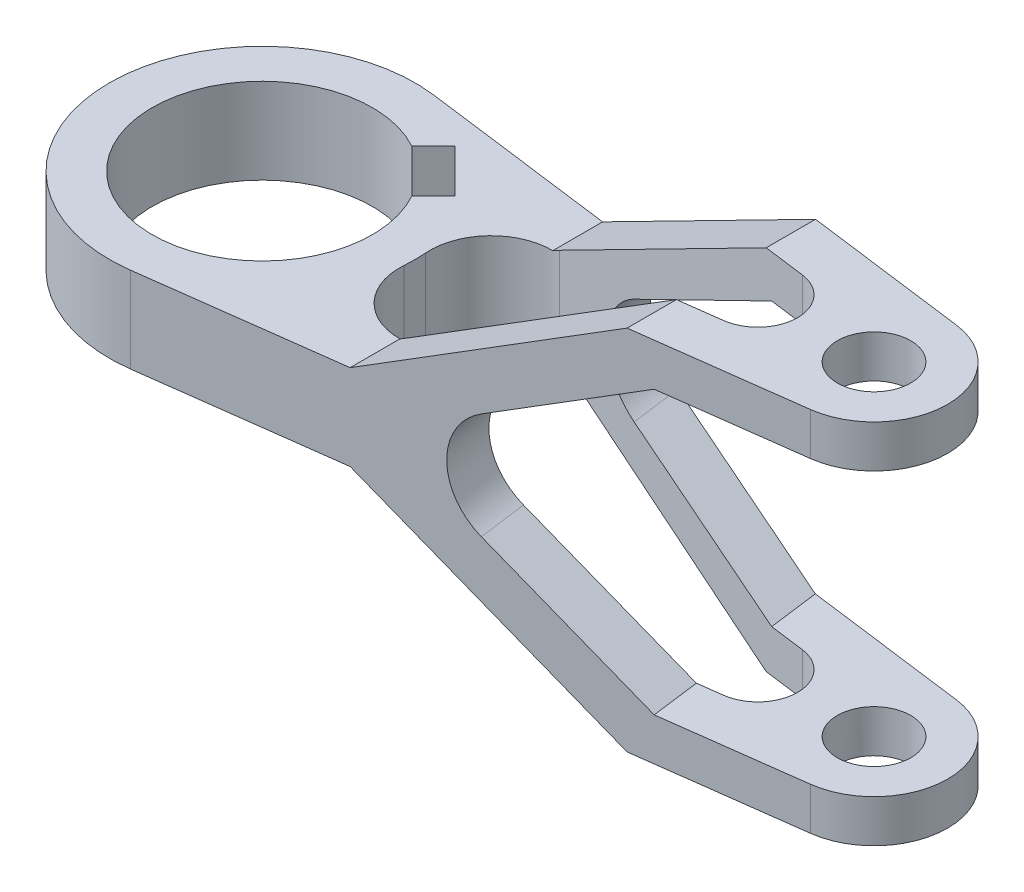
SolidWorks part; units mm, degrees
ref_plane "Front Plane" through (0, 0, 0) normal (0, 0, 1) x (1, 0, 0)
ref_plane "Top Plane" through (0, 0, 0) normal (0, 1, 0) x (1, 0, 0)
ref_plane "Right Plane" through (0, 0, 0) normal (1, 0, 0) x (0, 0, -1)
sketch "Sketch1" plane through (0, 0, 0) normal (0, 1, 0) x (1, 0, 0)
  line L0 (3.2407, 24.7891) -> (101.5604, 11.9355)
  line L1 (0, 0) -> (25, 0) construction
  line L2 (3.2407, -24.7891) -> (101.5604, -11.9355)
  line L3 (20.3793, 14.4804) -> (81.8426, 6.4452)
  line L4 (20.3793, -14.4804) -> (81.8426, -6.4452)
  line L5 (2.2037, 16.8566) -> (100.5233, 4.003) construction
  line L6 (2.2037, -16.8566) -> (100.5233, -4.003) construction
  line L7 (74.2692, 0) -> (88, 0) construction
  arc A0 (3.2407, 24.7891) -> (3.2407, -24.7891) centre (0, 0) ccw
  circle A2 centre (100, 0) radius 6
  circle A3 centre (0, 0) radius 18
  arc A4 (20.3793, -14.4804) -> (20.3793, 14.4804) centre (0, 0) ccw
  arc A5 (101.5604, -11.9355) -> (101.5604, 11.9355) centre (100, 0) ccw
  arc A6 (81.8426, -6.4452) -> (81.8426, 6.4452) centre (81, 0) ccw
  dimension "D2" = 50
  dimension "D3" = 19
  dimension "D4" = 36
  dimension "D5" = 12
  dimension "D8" = 13
  dimension "D1" = 100
  dimension "D6" = 8
  dimension "D7" = 8
extrude "Boss-Extrude2" add sketch "Sketch1" along normal blind 30 and the other way blind 30
sketch "Sketch3" plane through (0, 0, 0) normal (0, 0, 1) x (1, 0, 0)
  line L0 (-25, 7) -> (35, 7)
  line L1 (-25, 30) -> (-25, -30) construction
  line L2 (35, 7) -> (75.037, 30)
  line L3 (3.2407, 30) -> (101.5604, 30) construction
  line L4 (75.037, 30) -> (-25, 30)
  line L5 (-25, 30) -> (-25, 7)
  dimension "D1" = 7
  dimension "D2" = 60
  dimension "D3" = 37
extrude "Cut-Extrude1" cut sketch "Sketch3" against normal blind 30 and the other way up to next contours L4 L5 L0 L2
mirror "Mirror1" about plane through (0, 0, 0) normal (0, 1, 0) of "Cut-Extrude1"
sketch "Sketch4" plane through (3.2407, 0, 24.7891) normal (0.1296, 0, 0.9916) x (0.9916, 0, -0.1296)
  line L2 (35.9891, 0.0486) -> (76.3669, 23.0486)
  line L3 (51.1581, 8.6892) -> (76.3669, 23.0486)
  line L4 (76.3669, 23.0486) -> (111.1933, 23.0486)
  line L5 (35.9891, -0.0486) -> (76.3669, -23.0486)
  line L6 (51.1581, -8.6892) -> (76.3669, -23.0486)
  line L7 (111.1933, -30) -> (111.1933, 30) construction
  line L8 (111.1933, 23.0486) -> (111.1933, -23.0486)
  line L9 (111.1933, -23.0486) -> (76.3669, -23.0486)
  arc A0 (51.1581, -8.6892) -> (51.1581, 8.6892) centre (56.1076, 0) cw
  dimension "D3" = 10
  dimension "D1" = 8
  dimension "D2" = 8
extrude "Cut-Extrude3" cut sketch "Sketch4" against normal through all
fillet "Fillet1" radius 10 2 edges at (20.3793, 0, -14.4804) (20.3793, 0, 14.4804)
sketch "Sketch5" plane through (0, 7, 0) normal (0, 1, 0) x (1, 0, 0)
  line L0 (0, 0) -> (31.7682, 0) construction
  line L1 (15.7626, 15.7626) -> (16.0074, 16.0074) construction
  line L3 (8.6915, 15.7626) -> (12.227, 19.2981)
  line L5 (12.227, 19.2981) -> (19.2981, 12.227)
  line L6 (19.2981, 12.227) -> (15.7626, 8.6915)
  circle A0 centre (0, 0) radius 18 construction
  arc A1 (8.6915, 15.7626) -> (15.7626, 8.6915) centre (0, 0) ccw
  dimension "D1" = 45
  dimension "D2" = 5
  dimension "D3" = 5
  dimension "D4" = 5
extrude "Cut-Extrude4" cut sketch "Sketch5" against normal through all contours L5 L6 A1 L3
